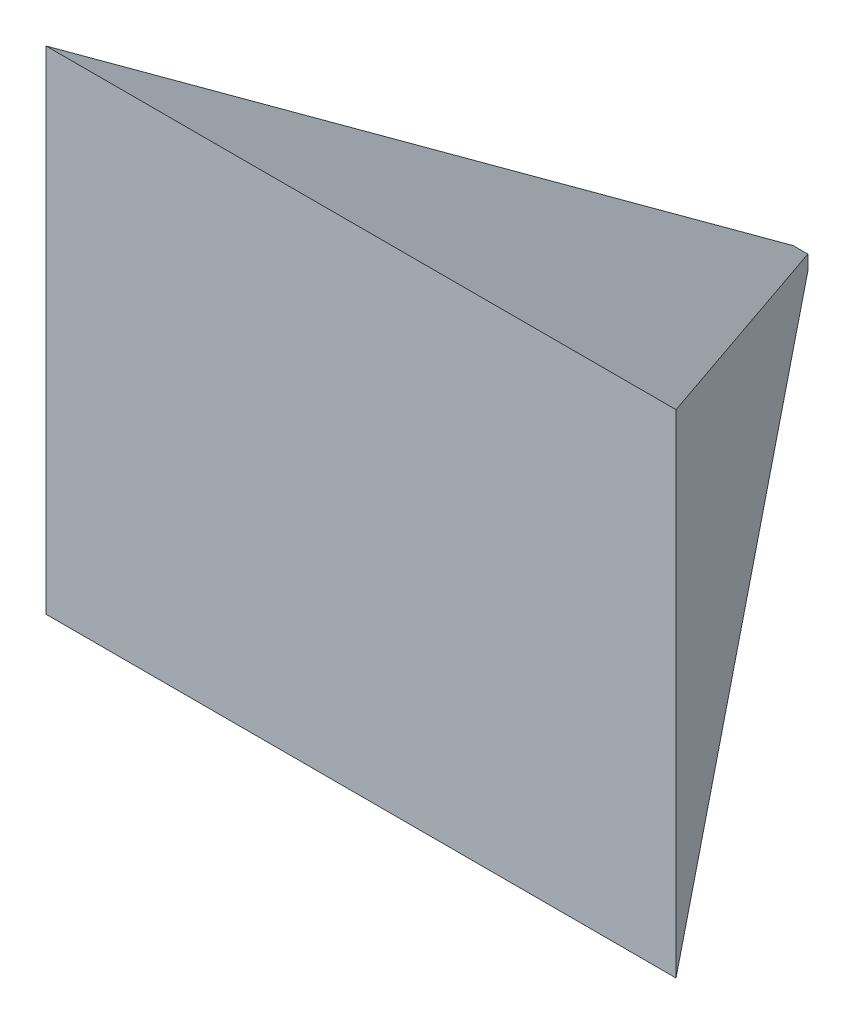
SolidWorks part; units mm, degrees
material "Acrylic (Medium-high impact)"
ref_plane "Front Plane" through (0, 0, 0) normal (0, 0, 1) x (1, 0, 0)
ref_plane "Top Plane" through (0, 0, 0) normal (0, 1, 0) x (1, 0, 0)
ref_plane "Right Plane" through (0, 0, 0) normal (1, 0, 0) x (0, 0, -1)
sketch "Sketch1" plane through (0, 0, 0) normal (0, 0, 1) x (1, 0, 0)
  line L0 (0, -5) -> (0, 5) construction
  line L1 (-5, 5) -> (5, 5)
  line L2 (-5, 5) -> (-5, -5)
  line L3 (-5, -5) -> (5, -5)
  line L4 (5, 5) -> (5, -5)
  line L5 (5, 0) -> (-5, 0) construction
  dimension "D1" = 10
  dimension "D2" = 10
ref_plane "Plane1" through (0, 0, 300) normal (0, 0, 1) x (1, 0, 0)
sketch "Sketch2" plane through (0, 0, 300) normal (0, 0, 1) x (1, 0, 0)
  line L0 (0, -168) -> (0, 0) construction
  line L1 (-215, 168) -> (215, 168)
  line L2 (-215, 168) -> (-215, -168)
  line L3 (-215, -168) -> (215, -168)
  line L4 (215, 168) -> (215, -168)
  line L5 (215, 0) -> (0, 0) construction
  dimension "D1" = 336
  dimension "D2" = 430
loft "Loft1" add profiles "Sketch1", "Sketch2" connector at (5, 5, 0) connector at (215, 168, 300)
